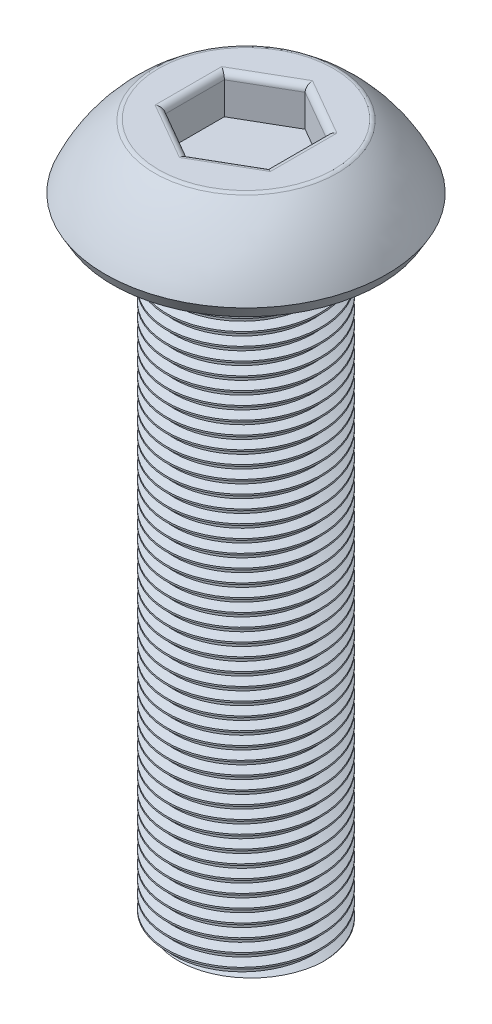
SolidWorks part; units mm, degrees
ref_plane "Front Plane" through (0, 0, 0) normal (0, 0, 1) x (1, 0, 0)
ref_plane "Top Plane" through (0, 0, 0) normal (0, 1, 0) x (1, 0, 0)
ref_plane "Right Plane" through (0, 0, 0) normal (1, 0, 0) x (0, 0, -1)
sketch "Sketch1" plane through (0, 0, 0) normal (1, 0, 0) x (0, 0, -1)
  line L0 (0, 0) -> (0, 1.5) construction
  line L1 (0, 1.5) -> (-1.75, 1.5)
  line L3 (-2.75, 0.25) -> (-2.6057, 0)
  line L4 (-2.6057, 0) -> (-1.5, 0)
  line L5 (-1.5, 0) -> (-1.5, -12)
  line L6 (-1.5, -12) -> (0, -12)
  line L7 (0, -12) -> (0, 1.5)
  line L8 (0, 0) -> (-1.5, 0) construction
  arc A0 (-1.75, 1.5) -> (-2.75, 0.25) centre (0.0077, -0.9312) ccw
  dimension "D5" = 3
  dimension "D1" = 1.5
  dimension "D2" = 2.75
  dimension "D3" = 1.75
  dimension "D4" = 0.25
  dimension "D6" = 60
  dimension "D7" = 1.5
  dimension "D8" = 12
revolve "Revolve1" add sketch "Sketch1" angle 360 about L7
sketch "Sketch2" plane through (0, 1.5, 0) normal (0, 1, 0) x (1, 0, 0)
  line L1 (0, 1.1547) -> (-1, 0.5774)
  line L2 (-1, 0.5774) -> (-1, -0.5774)
  line L3 (-1, -0.5774) -> (0, -1.1547)
  line L4 (0, -1.1547) -> (1, -0.5774)
  line L5 (1, -0.5774) -> (1, 0.5774)
  line L6 (1, 0.5774) -> (0, 1.1547)
  circle A0 centre (0, 0) radius 1 construction
  dimension "D1" = 2
extrude "Cut-Extrude1" cut sketch "Sketch2" against normal blind 0.75
fillet "Fillet1" radius 0.125 7 edges at (0, 1.5, -1.75) (-0.5, 1.5, 0.866) (0.5, 1.5, 0.866) (1, 1.5, 0) (0.5, 1.5, -0.866) (-0.5, 1.5, -0.866) (-1, 1.5, 0)
thread "Thread1" pitch 0.25 method cut profile "Thread Profile1" start angle 0, offset 1, length 12.75, pitch 0.25, diameter 3
ref_plane "Plane1" through (1.5, -13, 0) normal (0, 0, 1) x (1, 0, 0)
sketch "Thread Profile1" plane through (1.5, -13, 0) normal (0, 0, 1) x (1, 0, 0)
  line L0 (0, 0) -> (0, 0.25) construction
  line L11 (0, 0) -> (0, 0.2187)
  line L12 (0, 0.2187) -> (-0.1353, 0.1406)
  line L13 (-0.1353, 0.1406) -> (-0.1353, 0.0781)
  line L15 (-0.1353, 0.0781) -> (0, 0)
  line L17 (-0.1353, 0.1094) -> (0, 0.1094) construction
  point P2 (0, 0)
  dimension "Pitch" = 0.25
  dimension "Profile_Angle" = 60
  dimension "Profile_Land" = 0.0625
  dimension "Profile_Height" = 0.1353
